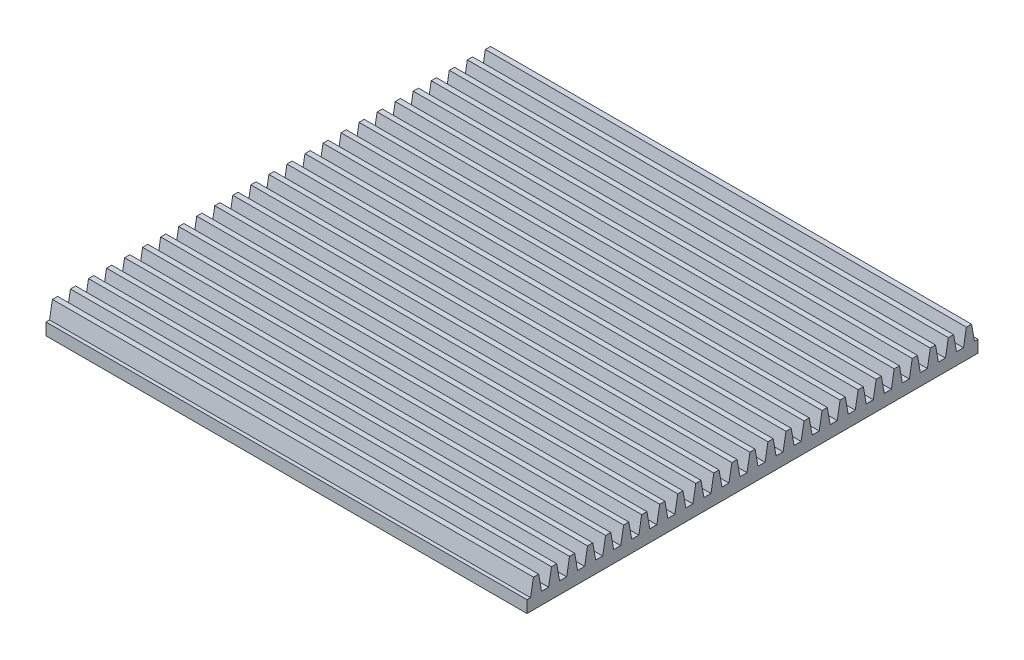
SolidWorks part; units mm, degrees
ref_plane "Front Plane" through (0, 0, 0) normal (0, 0, 1) x (1, 0, 0)
ref_plane "Top Plane" through (0, 0, 0) normal (0, 1, 0) x (1, 0, 0)
ref_plane "Right Plane" through (0, 0, 0) normal (1, 0, 0) x (0, 0, -1)
sketch "Sketch1" plane through (0, 0, 0) normal (1, 0, 0) x (0, 0, -1)
  line L0 (0, 0) -> (6, 0)
  line L1 (6, 0) -> (6, 4)
  line L2 (0, 4) -> (1.1735, 4)
  line L3 (1.1735, 4) -> (2.1317, 9.434)
  line L4 (2.1317, 9.434) -> (3.8683, 9.434)
  line L5 (0, 0) -> (0, 4)
  line L6 (3.8683, 9.434) -> (4.8265, 4)
  line L7 (4.8265, 4) -> (6, 4)
  point P3 (0, 0)
  dimension "D1" = 6
  dimension "D2" = 4
  dimension "D3" = 100
  dimension "D4" = 100
extrude "Boss-Extrude1" add sketch "Sketch1" along normal blind 160
pattern_linear "LPattern1" count 25 spacing 6 along (0, 0, -1) of "Boss-Extrude1"
